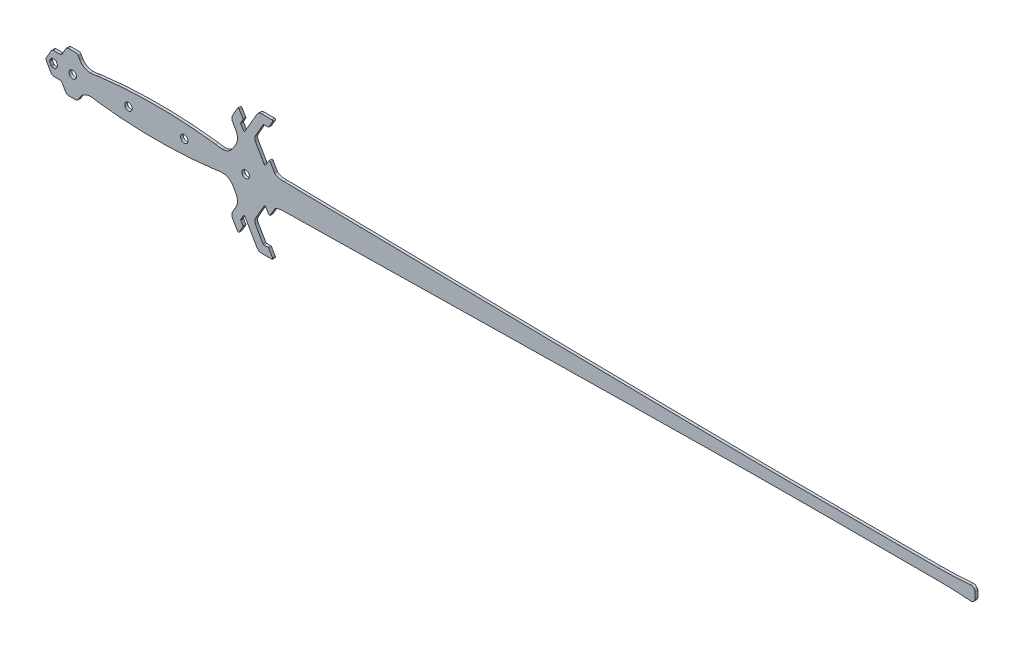
SolidWorks part; units mm, degrees
ref_plane "前视基准面" through (0, 0, 0) normal (0, 0, 1) x (1, 0, 0)
ref_plane "上视基准面" through (0, 0, 0) normal (0, 1, 0) x (1, 0, 0)
ref_plane "右视基准面" through (0, 0, 0) normal (1, 0, 0) x (0, 0, -1)
sketch "草图1" plane through (0, 0, 0) normal (0, 0, 1) x (1, 0, 0)
  line L0 (-50.3851, 0) -> (31.7426, 0) construction
  line L1 (0, 1048.2309) -> (0, 85.8209) construction
  line L2 (38, 14) -> (250, 10.5518)
  line L3 (-11.547, 12) -> (-1.547, 29.3205)
  line L4 (19.0526, 65) -> (35.0526, 65)
  line L5 (35.0526, 65) -> (29.8564, 56)
  line L6 (29.8564, 56) -> (24.2487, 56)
  line L7 (24.2487, 56) -> (14.1547, 38.5167)
  line L8 (14.1547, 38.5167) -> (26, 18)
  line L9 (26, 18) -> (30.8453, 26.3923)
  line L10 (30.8453, 26.3923) -> (38, 14)
  line L11 (-1.547, 29.3205) -> (-10.5996, 45)
  line L12 (3.6491, 38.3205) -> (-0.2073, 45)
  line L13 (-0.2073, 45) -> (2.5966, 49.8564)
  line L14 (2.5966, 49.8564) -> (-2.5996, 58.8564)
  line L15 (3.6491, 38.3205) -> (19.0526, 65)
  line L16 (-2.5996, 58.8564) -> (-10.5996, 45)
  line L17 (-90.7735, 16.1906) -> (-90.7735, 2.9968) construction
  line L18 (29.8564, -56) -> (24.2487, -56)
  line L19 (35.0526, -65) -> (29.8564, -56)
  line L20 (19.0526, -65) -> (35.0526, -65)
  line L21 (3.6491, -38.3205) -> (19.0526, -65)
  line L22 (24.2487, -56) -> (14.1547, -38.5167)
  line L23 (-170, 12) -> (-176.9282, 0)
  line L24 (-170, 12) -> (-175.7735, 22)
  line L25 (-175.7735, 22) -> (-187.2265, 22)
  line L26 (-187.2265, 22) -> (-193, 12)
  line L27 (-193, 12) -> (-203.0718, 12)
  line L28 (-203.0718, 12) -> (-210, 0)
  line L29 (-170, -12) -> (-176.9282, 0)
  line L30 (-203.0718, -12) -> (-210, 0)
  line L31 (-193, -12) -> (-203.0718, -12)
  line L32 (-187.2265, -22) -> (-193, -12)
  line L33 (-175.7735, -22) -> (-187.2265, -22)
  line L34 (-170, -12) -> (-175.7735, -22)
  line L35 (-11.547, -12) -> (-1.547, -29.3205)
  line L36 (0, 32) -> (3.6491, 38.3205) construction
  line L37 (-1.547, 29.3205) -> (0, 32) construction
  line L38 (-2.5996, -58.8564) -> (-10.5996, -45)
  line L39 (2.5966, -49.8564) -> (-2.5996, -58.8564)
  line L40 (-0.2073, -45) -> (2.5966, -49.8564)
  line L41 (640, 6) -> (750, 6)
  line L42 (790, 6) -> (790, -6) construction
  line L43 (640, -6) -> (750, -6)
  line L44 (38, -14) -> (250, -10.5518)
  line L45 (30.8453, -26.3923) -> (38, -14)
  line L46 (26, -18) -> (30.8453, -26.3923)
  line L47 (14.1547, -38.5167) -> (26, -18)
  line L48 (20.3038, 27.866) -> (14.6077, 18)
  line L49 (14.6077, 18) -> (25, 0)
  line L50 (14.6077, -18) -> (25, 0)
  line L51 (20.3038, -27.866) -> (14.6077, -18)
  line L52 (-206, 0) -> (-203.6906, 4)
  line L53 (-203.6906, 4) -> (-199.0718, 4)
  line L54 (-199.0718, 4) -> (-196.7624, 0)
  line L55 (-206, 0) -> (-203.6906, -4)
  line L56 (-203.6906, -4) -> (-199.0718, -4)
  line L57 (-199.0718, -4) -> (-196.7624, 0)
  line L58 (3.6491, -38.3205) -> (-0.2073, -45)
  line L59 (-1.547, -29.3205) -> (-10.5996, -45)
  line L60 (0, -32) -> (3.6491, -38.3205) construction
  line L61 (-1.547, -29.3205) -> (0, -32) construction
  line L62 (750, 6) -> (790.1637, 6) construction
  line L63 (790.1637, 6) -> (790, 6) construction
  line L64 (750, -6) -> (790.1637, -6) construction
  line L65 (790.1637, -6) -> (790, -6) construction
  arc A0 (-11.547, 12) -> (-27.547, 12) centre (-19.547, 43.5) cw
  arc A1 (-27.547, 12) -> (-154, 12) centre (-90.7735, -485.6987) ccw
  arc A2 (-27.547, -12) -> (-154, -12) centre (-90.7735, 485.6987) cw
  arc A3 (-11.547, -12) -> (-27.547, -12) centre (-19.547, -43.5) ccw
  arc A4 (-170, 12) -> (-154, 12) centre (-162, 43.5) ccw
  arc A5 (-170, -12) -> (-154, -12) centre (-162, -43.5) cw
  arc A6 (250, 10.5518) -> (490, 7) centre (1582.1102, 81911.6233) ccw
  arc A7 (490, 7) -> (640, 6) centre (640, 11256.5) ccw
  arc A8 (490, -7) -> (640, -6) centre (640, -11256.5) cw
  arc A9 (250, -10.5518) -> (490, -7) centre (1582.1102, -81911.6233) cw
  circle A10 centre (-120.7735, 0) radius 4.025
  circle A11 centre (-60.7735, 0) radius 4.025
  circle A12 centre (-180.7735, 0) radius 4.025
  circle A14 centre (5.2265, 0) radius 4.025
  arc A15 (750, 6) -> (784.8, 7.5) centre (750, 410.43) ccw
  arc A16 (784.8, 7.5) -> (789.7726, 3.5) centre (785.1971, 2.9028) cw
  arc A17 (789.7726, 3.5) -> (789.7726, -3.5) centre (762.957, 0) cw
  arc A18 (784.8, -7.5) -> (789.7726, -3.5) centre (785.1971, -2.9028) ccw
  arc A19 (750, -6) -> (784.8, -7.5) centre (750, -410.43) cw
  point P36 (-19.547, 11)
  point P37 (-19.547, -11)
  point P38 (-90.7735, 16)
  point P39 (-90.7735, -16)
  point P109 (771.5371, 15.2769)
  point P110 (780.7903, 9.4937)
  point P111 (787.503, 6)
  point P112 (787.6297, 6)
  point P113 (790, -1.7576)
  point P114 (789.9992, -2.4866)
  point P115 (0, 0)
  point P116 (0, 0)
  point P117 (0, 0)
  point P118 (0, 0)
  point P119 (789.9992, 2.4866)
  point P120 (789.9992, 2.4866)
  point P121 (789.612, -3.3221)
  point P122 (789.7716, -3.5)
  point P123 (784.7964, -7.5)
  point P124 (0, 0)
  dimension "D3" = 22
  dimension "D6" = 210
  dimension "D17" = 790
  dimension "D37" = 8.05
  dimension "D39" = 8.05
  dimension "D41" = 8.05
  dimension "D43" = 40
  dimension "D2" = 30
  dimension "D4" = 32
  dimension "D5" = 65
  dimension "D7" = 16
  dimension "D8" = 40
  dimension "D9" = 16
  dimension "D10" = 9
  dimension "D11" = 32
  dimension "D12" = 9
  dimension "D13" = 9
  dimension "D14" = 9
  dimension "D15" = 10
  dimension "D16" = 45
  dimension "D18" = 150
  dimension "D19" = 250
  dimension "D20" = 300
  dimension "D21" = 12
  dimension "D22" = 14
  dimension "D23" = 24
  dimension "D24" = 28
  dimension "D25" = 24
  dimension "D26" = 44
  dimension "D27" = 17
  dimension "D28" = 38
  dimension "D29" = 36
  dimension "D30" = 26
  dimension "D31" = 25
  dimension "D32" = 18
  dimension "D33" = 8
  dimension "D34" = 8
  dimension "D35" = 4
  dimension "D36" = 16
  dimension "D38" = 30
  dimension "D40" = 90
  dimension "D42" = 96
  dimension "D44" = 7
  dimension "D45" = 5.2
  dimension "D46" = 15
extrude "凸台-拉伸1" add sketch "草图1" along normal mid plane 3
fillet "圆角1" radius 13 6 edges at (-11.547, -12, 0) (-11.547, 12, 0) (-1.547, -29.3205, 0) (-1.547, 29.3205, 0) (-170, -12, 0) (-170, 12, 0)
fillet "圆角2" radius 6 6 edges at (19.0526, 65, 0) (19.0526, -65, 0) (14.1547, -38.5167, 0) (14.1547, 38.5167, 0) (-10.5996, 45, 0) (-10.5996, -45, 0)
fillet "圆角3" radius 1 24 edges at (24.2487, -56, 0) (24.2487, 56, 0) (35.0526, 65, 0) (29.8564, 56, 0) (35.0526, -65, 0) (29.8564, -56, 0) (26, -18, 0) (26, 18, 0) (30.8453, 26.3923, 0) (30.8453, -26.3923, 0) (-0.2073, -45, 0) (3.6491, -38.3205, 0) (3.6491, 38.3205, 0) (-0.2073, 45, 0) (-2.5996, 58.8564, 0) (2.5966, 49.8564, 0) (-2.5996, -58.8564, 0) (2.5966, -49.8564, 0) (-203.6906, -4, 0) (-199.0718, -4, 0) (-196.7624, 0, 0) (-199.0718, 4, 0) (-203.6906, 4, 0) (-206, 0, 0)
fillet "圆角5" radius 9 1 edges at (38, -14, 0)
fillet "圆角6" radius 9 1 edges at (38, 14, 0)
fillet "圆角7" radius 3 9 edges at (-175.7735, 22, 0) (-187.2265, 22, 0) (-193, 12, 0) (-203.0718, 12, 0) (-210, 0, 0) (-203.0718, -12, 0) (-193, -12, 0) (-187.2265, -22, 0) (-175.7735, -22, 0)
